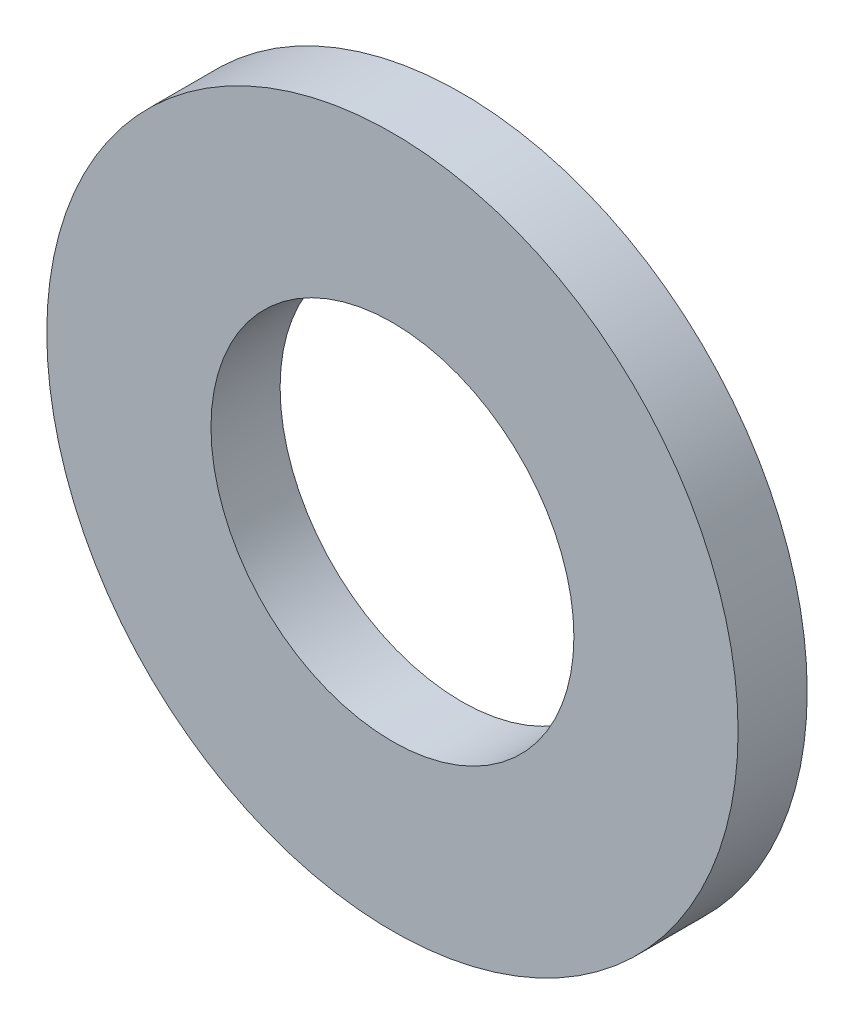
SolidWorks part; units mm, degrees
ref_plane "Plane1" through (0, 0, 0) normal (0, 0, 1) x (1, 0, 0)
ref_plane "Plane2" through (0, 0, 0) normal (0, 1, 0) x (1, 0, 0)
ref_plane "Plane3" through (0, 0, 0) normal (1, 0, 0) x (0, 0, -1)
sketch "Sketch1" plane through (0, 0, 0) normal (0, 0, 1) x (1, 0, 0)
  circle A0 centre (0, 0) radius 4.2
  circle A1 centre (0, 0) radius 8
  dimension "d1 Huldiameter" = 8.4
  dimension "d2 Udv.diameter" = 16
extrude "Base-Extrude" add sketch "Sketch1" along normal blind 1.6
sketch "Sketch2" [suppressed] plane through (0, 0, 1) normal (0, 0, 1) x (1, 0, 0)
  circle A0 centre (0, 15) radius 1.5
  dimension "D1" = 3
  dimension "D2" = 15
extrude "Cut-Extrude1" [suppressed] cut sketch "Sketch2" against normal through all
sketch "Sketch3" [suppressed] plane through (0, 0, 1) normal (0, 0, 1) x (1, 0, 0)
  circle A0 centre (0, 0) radius 19 construction
  circle A1 centre (0, 15) radius 1.5 construction
  circle A2 centre (0, 0) radius 11 construction
  circle A3 centre (0, 0) radius 19
  circle A4 centre (0, 15) radius 1.5
  circle A5 centre (0, 0) radius 11
extrude "Boss-Extrude3" [suppressed] add sketch "Sketch3" along normal blind 0.5
sketch "Sketch4" plane through (0, 0, 0) normal (0, 0, 1) x (1, 0, 0)
  line L0 (-2.5, -12.2474) -> (-2.5, -10.5)
  line L1 (-2.5, -10.5) -> (2.5, -10.5)
  line L2 (2.5, -10.5) -> (2.5, -12.2474)
  line L3 (0, 0) -> (0, -17.8897) construction
  arc A0 (2.5, -12.2474) -> (-2.5, -12.2474) centre (0, 0) ccw
  circle A1 centre (0, 0) radius 16
  dimension "d" = 25
  dimension "d1" = 32
  dimension "M" = 23
extrude "Extrude1" [suppressed] add sketch "Sketch4" along normal blind 1.25
sketch "Sketch5" [suppressed] plane through (0, 0, 0) normal (1, 0, 0) x (0, 0, -1)
  line L0 (0, -30.5) -> (0, -33.9729)
  line L1 (0, -33.5) -> (0, 33.5) construction
  line L2 (-0.1808, -34.5465) -> (-4.3495, -40.5)
  line L3 (-4.3495, -40.5) -> (-5.5782, -39.6396)
  line L4 (-5.5782, -39.6396) -> (-1.6808, -34.0736)
  line L5 (-1.5, -33.5) -> (-1.5, -30.5)
  line L6 (-1.5, -30.5) -> (0, -30.5)
  line L7 (-1.5, 33.5) -> (-1.5, -33.5) construction
  line L8 (0, 0) -> (-4.0582, 0) construction
  line L9 (-1.5, -33.5) -> (0, -33.5) construction
  arc A0 (-1.6808, -34.0736) -> (-1.5, -33.5) centre (-2.5, -33.5) ccw
  arc A1 (0, -33.9729) -> (-0.1808, -34.5465) centre (-1, -33.9729) cw
  dimension "D3" = 1
  dimension "d2" = 42
  dimension "D4" = 3
  dimension "D5" = 35
extrude "Extrude2" [suppressed] add sketch "Sketch5" along normal mid plane 5
pattern_circular "CirPattern1" [suppressed] count 13 over 360 of bodies 108
sketch "Sketch6" [suppressed] plane through (0, 0, 2.34) normal (0, 0, 1) x (1, 0, 0)
  line L0 (0, 7.5) -> (0, 14.1) construction
  line L1 (-1, 10.8) -> (-1, 7.433)
  line L2 (1, 10.8) -> (1, 7.433)
  circle A1 centre (0, 0) radius 7.5 construction
  circle A2 centre (0, 0) radius 14.1 construction
  arc A3 (1, 10.8) -> (-1, 10.8) centre (0, 10.8) ccw
  arc A4 (1, 7.433) -> (-1, 7.433) centre (0, 0) ccw
  point P9 (0, 10.8)
  dimension "D1" = 1
extrude "Cut-Extrude2" [suppressed] cut sketch "Sketch6" against normal through all
pattern_circular "CirPattern2" [suppressed] count 6 over 360 of bodies 112
